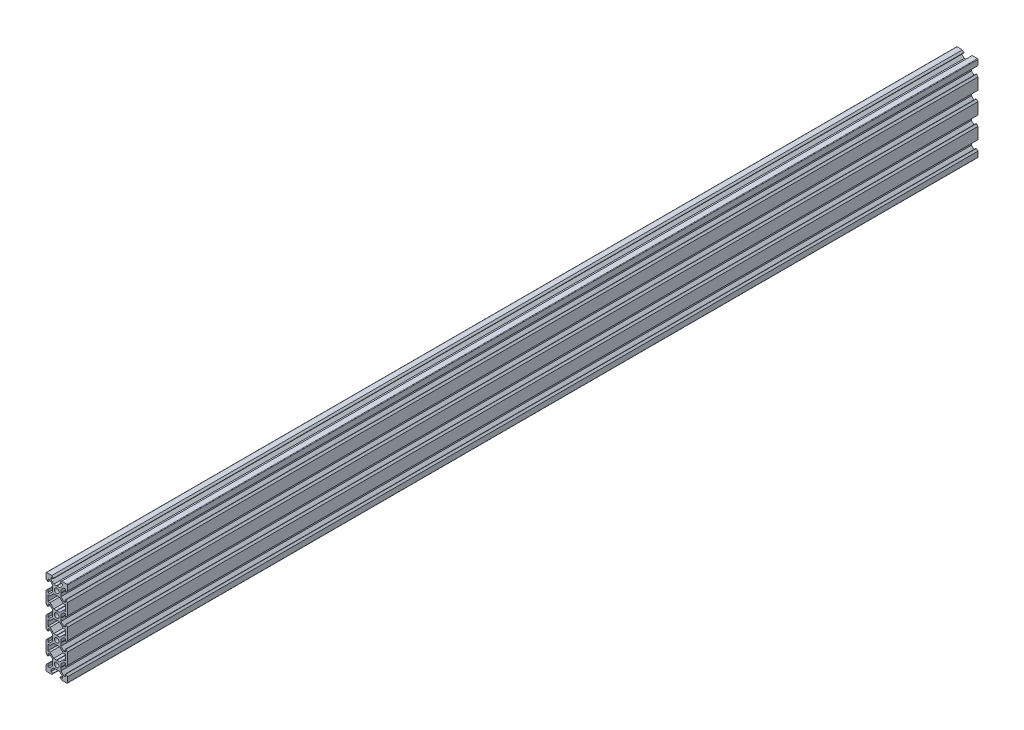
SolidWorks part; units mm, degrees
ref_plane "Plan de face" through (0, 0, 0) normal (0, 0, 1) x (1, 0, 0)
ref_plane "Plan de dessus" through (0, 0, 0) normal (0, 1, 0) x (1, 0, 0)
ref_plane "Plan de droite" through (0, 0, 0) normal (1, 0, 0) x (0, 0, -1)
ref_axis "Axe" through (0, 0, -13.782) along (0, 0, 1)
sketch "Esquisse1" plane through (0, 0, 0) normal (0, 0, 1) x (1, 0, 0)
  line L0 (0, 27.6392) -> (0, -27.6392) construction
  line L1 (-33.6074, 0) -> (33.6074, 0) construction
  line L2 (0, 0) -> (-22.2114, 22.2114) construction
  line L3 (-9.5, 10) -> (-4.58, 10)
  line L4 (-4.58, 10) -> (-3.125, 8.545)
  line L5 (-3.125, 8.545) -> (-3.125, 8.2)
  line L6 (-3.125, 8.2) -> (-5.5, 8.2)
  line L7 (-2.8393, 3.9) -> (-5.5, 6.5607)
  line L8 (-2.8393, 3.9) -> (-0.21, 3.9)
  line L9 (-5.5, 6.5607) -> (-5.5, 8.2)
  line L10 (0, 3.69) -> (0, 2.1)
  line L11 (-3.9, 2.8393) -> (-6.5607, 5.5)
  line L12 (-8.545, 3.125) -> (-8.2, 3.125)
  line L13 (-8.2, 3.125) -> (-8.2, 5.5)
  line L14 (-6.5607, 5.5) -> (-8.2, 5.5)
  line L15 (-10, 4.58) -> (-8.545, 3.125)
  line L16 (-10, 9.5) -> (-10, 4.58)
  line L17 (-0.21, 3.9) -> (0, 3.69)
  line L18 (-3.9, 2.8393) -> (-3.9, 0.21)
  line L19 (-6.2393, -12.7) -> (-8.2, -12.7)
  line L20 (-3.9, 0.21) -> (-3.69, 0)
  line L21 (-0.21, -3.9) -> (0, -3.69)
  line L22 (0, -3.69) -> (0, -2.1)
  line L23 (-6.5607, -5.5) -> (-8.2, -5.5)
  line L24 (-2.8393, -3.9) -> (-0.21, -3.9)
  line L25 (-8.545, -3.125) -> (-8.2, -3.125)
  line L26 (-10, -4.58) -> (-8.545, -3.125)
  line L27 (-8.2, -3.125) -> (-8.2, -5.5)
  line L28 (-2.8393, -3.9) -> (-6.2393, -7.3)
  line L29 (-3.9, -2.8393) -> (-6.5607, -5.5)
  line L30 (-3.9, -2.8393) -> (-3.9, -0.21)
  line L31 (-3.9, -0.21) -> (-3.69, 0)
  line L32 (-6.2393, -7.3) -> (-8.2, -7.3)
  line L33 (-8.2, -7.3) -> (-8.2, -12.7)
  line L34 (-8.2, -10) -> (-10, -10) construction
  line L35 (-10, -15.42) -> (-10, -4.58)
  line L36 (-3.9, -19.79) -> (-3.69, -20)
  line L37 (-3.9, -17.1607) -> (-3.9, -19.79)
  line L38 (-3.9, -17.1607) -> (-6.5607, -14.5)
  line L39 (-2.8393, -16.1) -> (-6.2393, -12.7)
  line L40 (-8.2, -16.875) -> (-8.2, -14.5)
  line L41 (-10, -15.42) -> (-8.545, -16.875)
  line L42 (-8.545, -16.875) -> (-8.2, -16.875)
  line L43 (-2.8393, -16.1) -> (-0.21, -16.1)
  line L44 (-6.5607, -14.5) -> (-8.2, -14.5)
  line L45 (0, -16.31) -> (0, -17.9)
  line L46 (-0.21, -16.1) -> (0, -16.31)
  line L47 (-8.2, -30) -> (-10, -30) construction
  line L48 (-3.69, -20) -> (0, -20) construction
  line L49 (-0.21, -23.9) -> (0, -23.69)
  line L50 (0, -23.69) -> (0, -22.1)
  line L51 (-6.5607, -25.5) -> (-8.2, -25.5)
  line L52 (-2.8393, -23.9) -> (-0.21, -23.9)
  line L53 (-8.545, -23.125) -> (-8.2, -23.125)
  line L54 (-10, -24.58) -> (-8.545, -23.125)
  line L55 (-8.2, -23.125) -> (-8.2, -25.5)
  line L56 (-2.8393, -23.9) -> (-6.2393, -27.3)
  line L57 (-3.9, -22.8393) -> (-6.5607, -25.5)
  line L58 (-3.9, -22.8393) -> (-3.9, -20.21)
  line L59 (-3.9, -20.21) -> (-3.69, -20)
  line L60 (-10, -24.58) -> (-10, -35.42)
  line L61 (-8.2, -32.7) -> (-8.2, -27.3)
  line L62 (-3.69, -40) -> (0, -40) construction
  line L63 (-8.2, -50) -> (-10, -50) construction
  line L64 (0, -60) -> (-22.2114, -82.2114) construction
  line L65 (-33.6074, -60) -> (33.6074, -60) construction
  line L66 (0, -87.6392) -> (0, -32.3608) construction
  line L67 (-6.2393, -32.7) -> (-8.2, -32.7)
  line L68 (-3.9, -39.79) -> (-3.69, -40)
  line L69 (-3.9, -37.1607) -> (-3.9, -39.79)
  line L70 (-3.9, -37.1607) -> (-6.5607, -34.5)
  line L71 (-2.8393, -36.1) -> (-6.2393, -32.7)
  line L72 (-8.2, -36.875) -> (-8.2, -34.5)
  line L73 (-10, -35.42) -> (-8.545, -36.875)
  line L74 (-8.545, -36.875) -> (-8.2, -36.875)
  line L75 (-6.2393, -27.3) -> (-8.2, -27.3)
  line L76 (-2.8393, -36.1) -> (-0.21, -36.1)
  line L77 (-6.5607, -34.5) -> (-8.2, -34.5)
  line L78 (0, -36.31) -> (0, -37.9)
  line L79 (-0.21, -36.1) -> (0, -36.31)
  line L80 (-0.21, -43.9) -> (0, -43.69)
  line L81 (0, -43.69) -> (0, -42.1)
  line L82 (-6.5607, -45.5) -> (-8.2, -45.5)
  line L83 (-2.8393, -43.9) -> (-0.21, -43.9)
  line L84 (-8.545, -43.125) -> (-8.2, -43.125)
  line L85 (-10, -44.58) -> (-8.545, -43.125)
  line L86 (-8.2, -43.125) -> (-8.2, -45.5)
  line L87 (-2.8393, -43.9) -> (-6.2393, -47.3)
  line L88 (-3.9, -42.8393) -> (-6.5607, -45.5)
  line L89 (-3.9, -42.8393) -> (-3.9, -40.21)
  line L90 (-3.9, -40.21) -> (-3.69, -40)
  line L91 (-10, -44.58) -> (-10, -55.42)
  line L92 (-8.2, -52.7) -> (-8.2, -47.3)
  line L93 (-6.2393, -52.7) -> (-8.2, -52.7)
  line L94 (-3.9, -59.79) -> (-3.69, -60)
  line L95 (-3.9, -57.1607) -> (-3.9, -59.79)
  line L96 (-3.9, -57.1607) -> (-6.5607, -54.5)
  line L97 (-2.8393, -56.1) -> (-6.2393, -52.7)
  line L98 (-8.2, -56.875) -> (-8.2, -54.5)
  line L99 (-10, -55.42) -> (-8.545, -56.875)
  line L100 (-8.545, -56.875) -> (-8.2, -56.875)
  line L101 (-2.8393, -56.1) -> (-0.21, -56.1)
  line L102 (-6.5607, -54.5) -> (-8.2, -54.5)
  line L103 (0, -56.31) -> (0, -57.9)
  line L104 (-0.21, -56.1) -> (0, -56.31)
  line L105 (-3.9, -60.21) -> (-3.69, -60)
  line L106 (-6.2393, -47.3) -> (-8.2, -47.3)
  line L107 (-3.9, -62.8393) -> (-3.9, -60.21)
  line L108 (-0.21, -63.9) -> (0, -63.69)
  line L109 (-10, -69.5) -> (-10, -64.58)
  line L110 (-10, -64.58) -> (-8.545, -63.125)
  line L111 (-6.5607, -65.5) -> (-8.2, -65.5)
  line L112 (-8.2, -63.125) -> (-8.2, -65.5)
  line L113 (-8.545, -63.125) -> (-8.2, -63.125)
  line L114 (-3.9, -62.8393) -> (-6.5607, -65.5)
  line L115 (0, -63.69) -> (0, -62.1)
  line L116 (-5.5, -66.5607) -> (-5.5, -68.2)
  line L117 (-2.8393, -63.9) -> (-0.21, -63.9)
  line L118 (-2.8393, -63.9) -> (-5.5, -66.5607)
  line L119 (-3.125, -68.2) -> (-5.5, -68.2)
  line L120 (-3.125, -68.545) -> (-3.125, -68.2)
  line L121 (-4.58, -70) -> (-3.125, -68.545)
  line L122 (-9.5, -70) -> (-4.58, -70)
  arc A0 (0, -2.1) -> (0, 2.1) centre (0, 0) cw
  arc A1 (-9.5, 10) -> (-10, 9.5) centre (-9.5, 9.5) ccw
  arc A2 (0, -42.1) -> (0, -37.9) centre (0, -40) cw
  arc A3 (-9.5, -70) -> (-10, -69.5) centre (-9.5, -69.5) cw
  arc A4 (0, -17.9) -> (0, -22.1) centre (0, -20) ccw
  arc A5 (0, -57.9) -> (0, -62.1) centre (0, -60) ccw
  point P4 (0, 0)
  point P7 (0, 0)
  point P30 (-10, 10)
  point P60 (0, -20)
  point P146 (-10, -70)
  dimension "D5" = 11
  dimension "D2" = 2.1
  dimension "D3" = 6.25
  dimension "D10" = 0.5
  dimension "D4" = 9.16
  dimension "D6" = 1.5
  dimension "D7" = 1.8
  dimension "D8" = 4.3
  dimension "D9" = 20
  dimension "D11" = 0.42
  dimension "D12" = 10
  dimension "D13" = 1.8
extrude "Boss.-Extru.1" add sketch "Esquisse1" along normal blind 850
sketch "Esquisse3" plane through (0, 0, 850) normal (0, 0, 1) x (1, 0, 0)
  line L0 (0, 0) -> (-9.8536, 9.8536) construction
  line L1 (-8.2, 8.2) -> (-8.2, 6.57)
  line L2 (-8.2, 6.57) -> (-7.54, 6.57)
  line L3 (-7.54, 6.57) -> (-6.57, 7.54)
  line L4 (-8.2, 3.125) -> (-8.2, 5.5) construction
  line L5 (-6.57, 8.2) -> (-6.57, 7.54)
  line L6 (-8.2, 8.2) -> (-6.57, 8.2)
  line L7 (-5.5, 6.5607) -> (-5.5, 8.2) construction
  line L8 (-10, -30) -> (6.918, -30) construction
  line L9 (-10, -24.58) -> (-10, -35.42) construction
  line L10 (-8.2, -68.2) -> (-6.57, -68.2)
  line L11 (-6.57, -68.2) -> (-6.57, -67.54)
  line L12 (-7.54, -66.57) -> (-6.57, -67.54)
  line L13 (-8.2, -66.57) -> (-7.54, -66.57)
  line L14 (-8.2, -68.2) -> (-8.2, -66.57)
  arc A0 (-9.5, 10) -> (-10, 9.5) centre (-9.5, 9.5) ccw construction
  point P13 (-7.055, 7.055)
  point P14 (-6.57, 7.87)
  point P26 (-7.055, -67.055)
  dimension "D1" = 1.07
extrude "Enlèv. mat.-Extru.1" [suppressed] cut sketch "Esquisse3" against normal through all
mirror "Symétrie1" about plane through (0, 3.69, 850) normal (-1, 0, 0) of "Enlèv. mat.-Extru.1", "Boss.-Extru.1"
